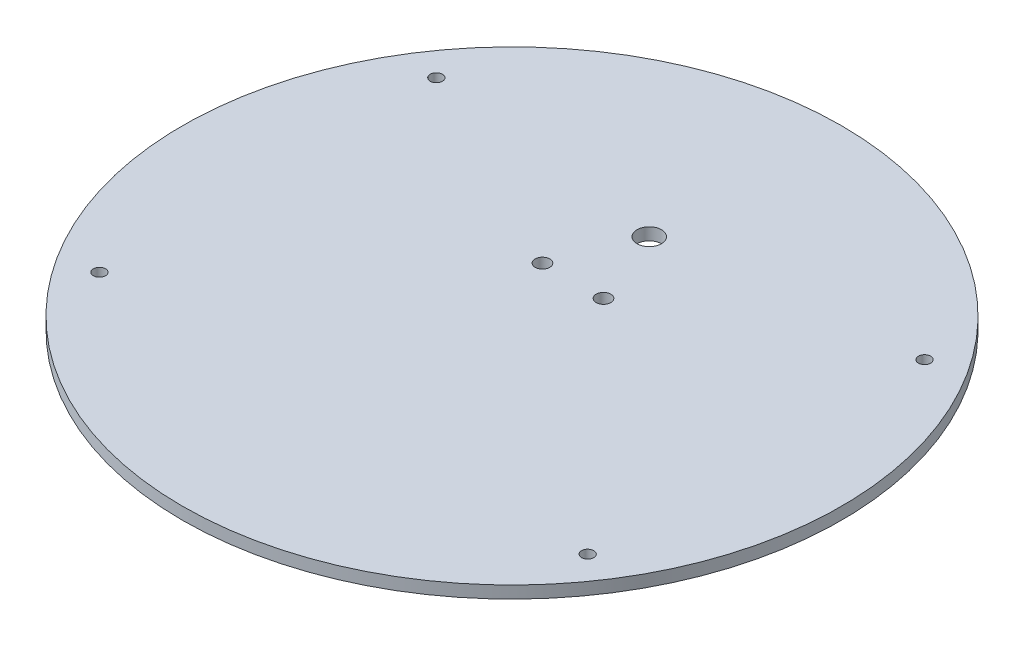
SolidWorks part; units mm, degrees
ref_plane "Front Plane" through (0, 0, 0) normal (0, 0, 1) x (1, 0, 0)
ref_plane "Top Plane" through (0, 0, 0) normal (0, 1, 0) x (1, 0, 0)
ref_plane "Right Plane" through (0, 0, 0) normal (1, 0, 0) x (0, 0, -1)
sketch "Sketch1" plane through (0, 0, 0) normal (0, 1, 0) x (1, 0, 0)
  circle A0 centre (0, 0) radius 85.725
  dimension "D1" = 171.45
extrude "Boss-Extrude1" add sketch "Sketch1" along normal blind 3.175
sketch "Sketch2" plane through (0, 3.175, 0) normal (0, 1, 0) x (1, 0, 0)
  line L0 (-63.5, 43.815) -> (-63.5, -43.815) construction
  line L1 (-63.5, -43.815) -> (63.5, -43.815) construction
  line L2 (63.5, -43.815) -> (63.5, 43.815) construction
  line L3 (63.5, 43.815) -> (-63.5, 43.815) construction
  circle A0 centre (-63.5, 43.815) radius 1.5875
  circle A1 centre (63.5, 43.815) radius 1.5875
  circle A2 centre (-63.5, -43.815) radius 1.5875
  circle A3 centre (63.5, -43.815) radius 1.5875
  dimension "D1" = 3.175
  dimension "D2" = 3.175
  dimension "D3" = 127
  dimension "D4" = 3.175
  dimension "D5" = 3.175
  dimension "D6" = 87.63
  dimension "D7" = 87.63
  dimension "D8" = 43.815
  dimension "D9" = 63.5
extrude "Cut-Extrude1" cut sketch "Sketch2" against normal up to next
sketch "Sketch3" plane through (0, 3.175, 0) normal (0, 1, 0) x (1, 0, 0)
  line L0 (0, 35.7022) -> (0, 0) construction
  circle A0 centre (0, 35.7022) radius 3.175
  dimension "D1" = 6.35
  dimension "D2" = 35.7022
extrude "Cut-Extrude2" cut sketch "Sketch3" against normal up to next contours A0
ref_axis "Axis1" through (0, 3.175, 0) along (0, -1, 0)
sketch "Sketch4" plane through (0, 0, 0) normal (0, -1, 0) x (1, 0, 0)
  line L0 (-7.9375, -15.8585) -> (7.9375, -15.8585) construction
  circle A2 centre (-7.9375, -15.8585) radius 1.905
  circle A3 centre (7.9375, -15.8585) radius 1.905
  circle A4 centre (0, -35.7022) radius 3.175 construction
  dimension "D2" = 3.81
  dimension "D3" = 3.81
  dimension "D1" = 19.8438
extrude "Cut-Extrude3" cut sketch "Sketch4" against normal up to next
